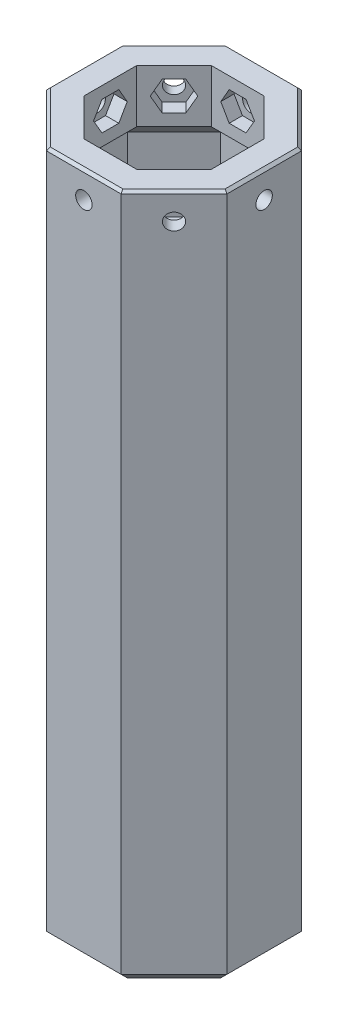
SolidWorks part; units mm, degrees
ref_plane "Alzado" through (0, 0, 0) normal (0, 0, 1) x (1, 0, 0)
ref_plane "Planta" through (0, 0, 0) normal (0, 1, 0) x (1, 0, 0)
ref_plane "Vista lateral" through (0, 0, 0) normal (1, 0, 0) x (0, 0, -1)
sketch "Croquis1" plane through (0, 0, 0) normal (0, 1, 0) x (1, 0, 0)
  line L0 (0, 0) -> (0, 30.3027) construction
  line L1 (17, -7.0416) -> (17, 7.0416)
  line L2 (17, 7.0416) -> (7.0416, 17)
  line L3 (7.0416, 17) -> (-7.0416, 17)
  line L4 (-7.0416, 17) -> (-17, 7.0416)
  line L5 (-17, 7.0416) -> (-17, -7.0416)
  line L6 (-17, -7.0416) -> (-7.0416, -17)
  line L7 (-7.0416, -17) -> (7.0416, -17)
  line L8 (7.0416, -17) -> (17, -7.0416)
  circle A0 centre (0, 0) radius 17 construction
  circle A1 centre (0, 11) radius 1.55
  circle A2 centre (0, 0) radius 4
  circle A3 centre (7.7782, 7.7782) radius 1.55
  circle A4 centre (11, 0) radius 1.55
  circle A5 centre (7.7782, -7.7782) radius 1.55
  circle A6 centre (0, -11) radius 1.55
  circle A7 centre (-7.7782, -7.7782) radius 1.55
  circle A8 centre (-11, 0) radius 1.55
  circle A9 centre (-7.7782, 7.7782) radius 1.55
  point P32 (0, 0)
  dimension "D1" = 34
  dimension "D2" = 3.1
  dimension "D3" = 11
  dimension "D4" = 8
  dimension "D5" = 8
extrude "Saliente-Extruir1" add sketch "Croquis1" along normal blind 120
sketch "Croquis2" plane through (0, 120, 0) normal (0, 1, 0) x (1, 0, 0)
  line L0 (7.0416, 17) -> (-7.0416, 17) construction
  line L1 (6.2132, 15) -> (-6.2132, 15)
  line L2 (-6.2132, 15) -> (-15, 6.2132)
  line L3 (-15, 6.2132) -> (-15, -6.2132)
  line L4 (-15, -6.2132) -> (-6.2132, -15)
  line L5 (-6.2132, -15) -> (6.2132, -15)
  line L6 (6.2132, -15) -> (15, -6.2132)
  line L7 (15, -6.2132) -> (15, 6.2132)
  line L8 (15, 6.2132) -> (6.2132, 15)
  line L9 (-17, 7.0416) -> (-17, -7.0416) construction
  circle A0 centre (0, 0) radius 15 construction
  dimension "D1" = 2
extrude "Cortar-Extruir1" cut sketch "Croquis2" against normal offset from surface (117 mm away) 3 up to face at (0, 0, 0)
sketch "Croquis3" plane through (0, 120, 0) normal (0, 1, 0) x (1, 0, 0)
  line L1 (12, -4.9706) -> (12, 4.9706)
  line L2 (12, 4.9706) -> (4.9706, 12)
  line L3 (4.9706, 12) -> (-4.9706, 12)
  line L4 (-4.9706, 12) -> (-12, 4.9706)
  line L5 (-12, 4.9706) -> (-12, -4.9706)
  line L6 (-12, -4.9706) -> (-4.9706, -12)
  line L7 (-4.9706, -12) -> (4.9706, -12)
  line L8 (4.9706, -12) -> (12, -4.9706)
  line L9 (7.0416, 17) -> (-7.0416, 17)
  line L10 (-7.0416, 17) -> (-17, 7.0416)
  line L11 (-17, 7.0416) -> (-17, -7.0416)
  line L12 (-17, -7.0416) -> (-7.0416, -17)
  line L13 (-7.0416, -17) -> (7.0416, -17)
  line L14 (7.0416, -17) -> (17, -7.0416)
  line L15 (17, -7.0416) -> (17, 7.0416)
  line L16 (17, 7.0416) -> (7.0416, 17)
  circle A0 centre (0, 0) radius 12 construction
  circle A1 centre (0, 0) radius 17 construction
  dimension "D1" = 5
extrude "Saliente-Extruir2" add sketch "Croquis3" along normal blind 10
chamfer "Chaflán2" distance 3 angle 45 8 edges at (-10.6066, 120, 10.6066) (0, 120, 15) (10.6066, 120, 10.6066) (15, 120, 0) (10.6066, 120, -10.6066) (0, 120, -15) (-10.6066, 120, -10.6066) (-15, 120, 0)
sketch "Croquis4" plane through (-12.0208, 0, -12.0208) normal (-0.7071, 0, -0.7071) x (-0.7071, 0, 0.7071)
  line L0 (-7.0416, 130) -> (7.0416, 130) construction
  circle A0 centre (0, 125) radius 1.55
  dimension "D1" = 3.1
  dimension "D2" = 5
extrude "Cortar-Extruir2" cut sketch "Croquis4" against normal up to next
chamfer "Chaflán3" distance 0.5 angle 45 1 edges at (-13.1168, 125, -10.9248)
sketch "Croquis5" plane through (-12.0208, 0, -12.0208) normal (-0.7071, 0, -0.7071) x (-0.7071, 0, 0.7071)
  line L1 (3.1754, 125) -> (1.5877, 127.75)
  line L2 (1.5877, 127.75) -> (-1.5877, 127.75)
  line L3 (-1.5877, 127.75) -> (-3.1754, 125)
  line L4 (-3.1754, 125) -> (-1.5877, 122.25)
  line L5 (-1.5877, 122.25) -> (1.5877, 122.25)
  line L6 (1.5877, 122.25) -> (3.1754, 125)
  circle A0 centre (0, 125) radius 2.75 construction
  dimension "D1" = 5.5
extrude "Cortar-Extruir3" cut sketch "Croquis5" against normal blind 10 from offset 2.5 offset against normal yes
pattern_circular "MatrizC5" count 8 over 360 about axis through (0, 3, 0) along (0, 1, 0) of "Cortar-Extruir2", "Cortar-Extruir3"
chamfer "Chaflán1" distance 2 angle 45 8 edges at (0, 0, 17) (-12.0208, 0, 12.0208) (-17, 0, 0) (-12.0208, 0, -12.0208) (0, 0, -17) (12.0208, 0, -12.0208) (17, 0, 0) (12.0208, 0, 12.0208)
chamfer "Chaflán4" distance 0.5 angle 45 8 edges at (12.0208, 130, -12.0208) (0, 130, -17) (-12.0208, 130, -12.0208) (-17, 130, 0) (-12.0208, 130, 12.0208) (0, 130, 17) (12.0208, 130, 12.0208) (17, 130, 0)
